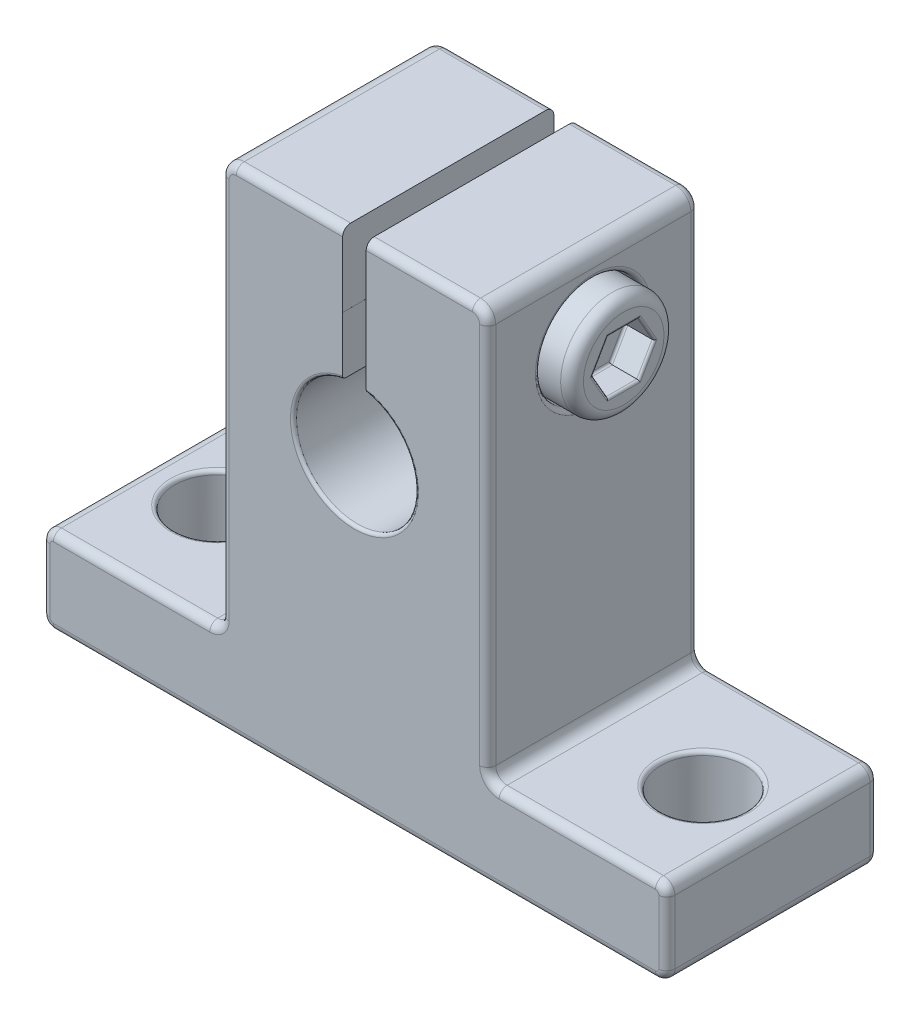
SolidWorks part; units mm, degrees
ref_plane "Plano frontal" through (0, 0, 0) normal (0, 0, 1) x (1, 0, 0)
ref_plane "Plano superior" through (0, 0, 0) normal (0, 1, 0) x (1, 0, 0)
ref_plane "Plano direito" through (0, 0, 0) normal (1, 0, 0) x (0, 0, -1)
sketch "Esboço1" plane through (0, 0, 0) normal (0, 0, 1) x (1, 0, 0)
  line L0 (-7.7757, 16.3) -> (-0.7757, 16.3)
  line L1 (-19.815, -16.3) -> (19.815, -16.3)
  line L2 (-20.565, -15.55) -> (-20.565, -11.35)
  line L3 (-19.815, -10.6) -> (-9.5257, -10.6)
  line L4 (20.565, -15.55) -> (20.565, -11.35)
  line L5 (0.7743, 16.3) -> (7.7743, 16.3)
  line L6 (9.5243, -10.6) -> (19.815, -10.6)
  line L7 (8.7743, 15.3) -> (8.7743, -9.85)
  line L8 (-8.7757, 15.3) -> (-8.7757, -9.85)
  line L10 (-0.7757, 11.4644) -> (-0.7757, 16.3)
  line L12 (0.7743, 11.4644) -> (0.7743, 16.3)
  arc A0 (8.7743, 15.3) -> (7.7743, 16.3) centre (7.7743, 15.3) ccw
  arc A1 (-7.7757, 16.3) -> (-8.7757, 15.3) centre (-7.7757, 15.3) ccw
  arc A2 (-20.565, -15.55) -> (-19.815, -16.3) centre (-19.815, -15.55) ccw
  arc A3 (-20.565, -11.35) -> (-19.815, -10.6) centre (-19.815, -11.35) cw
  arc A4 (19.815, -10.6) -> (20.565, -11.35) centre (19.815, -11.35) cw
  arc A5 (19.815, -16.3) -> (20.565, -15.55) centre (19.815, -15.55) ccw
  arc A6 (8.7743, -9.85) -> (9.5243, -10.6) centre (9.5243, -9.85) ccw
  arc A7 (-8.7757, -9.85) -> (-9.5257, -10.6) centre (-9.5257, -9.85) cw
  arc A8 (-0.7757, 11.4644) -> (0.7743, 11.4644) centre (-0.0007, 7.53) ccw
  point P0 (0, 0)
  point P9 (8.7743, 16.3)
  point P15 (-8.7757, 16.3)
  point P18 (-20.565, -16.3)
  point P23 (20.565, -10.6)
  point P26 (20.565, -16.3)
  point P29 (8.7743, -10.6)
  dimension "D1" = 1
  dimension "D4" = 0.75
  dimension "D6" = 8.02
  dimension "D2" = 41.13
  dimension "D3" = 17.55
  dimension "D5" = 5.7
extrude "Ressalto-extrusão1" add sketch "Esboço1" along normal blind 13.9
fillet "Filete2" radius 0.53 34 edges at (-4.2757, 16.3, 13.9) (-8.4828, 16.0071, 13.9) (4.2743, 16.3, 13.9) (8.4814, 16.0071, 13.9) (8.7743, 2.725, 13.9) (8.994, -10.3803, 13.9) (14.6697, -10.6, 13.9) (20.3453, -10.8197, 13.9) (20.565, -13.45, 13.9) (20.3453, -16.0803, 13.9) (0, -16.3, 13.9) (-20.3453, -16.0803, 13.9) (-20.565, -13.45, 13.9) (-20.3453, -10.8197, 13.9) (-14.6703, -10.6, 13.9) (-8.9954, -10.3803, 13.9) (-4.2757, 16.3, 0) (-8.4828, 16.0071, 0) (4.2743, 16.3, 0) (8.4814, 16.0071, 0) (8.7743, 2.725, 0) (8.994, -10.3803, 0) (14.6697, -10.6, 0) (20.3453, -10.8197, 0) (20.565, -13.45, 0) (20.3453, -16.0803, 0) (0, -16.3, 0) (-20.3453, -16.0803, 0) (-20.565, -13.45, 0) (-20.3453, -10.8197, 0) (-14.6703, -10.6, 0) (-8.9954, -10.3803, 0) (-8.7757, 2.725, 13.9) (-8.7757, 2.725, 0)
sketch "Esboço9" plane through (0, 0, 0) normal (0, 0, -1) x (-1, 0, 0)
  circle A1 centre (0.0007, 7.53) radius 4.01
extrude "Ressalto-extrusão4" add sketch "Esboço9" against normal blind 13.9
sketch "Esboço10" plane through (0, 0, 13.9) normal (0, 0, 1) x (1, 0, 0)
  line L0 (-0.7743, 16.3) -> (-0.7743, 7.6445)
  line L1 (0.7743, 11.4644) -> (0.7743, 7.6445)
  line L3 (-0.7743, 16.3) -> (0.7743, 16.3)
  line L4 (0.7743, 11.4644) -> (0.7743, 16.3)
  line L5 (0.7743, 11.4644) -> (0.7743, 16.3)
  line L8 (0.7743, 11.4644) -> (0.7743, 16.3)
  arc A0 (-0.7743, 7.6445) -> (0.7743, 7.6445) centre (0, 3.71) ccw
  dimension "D1" = 8.02
extrude "Corte-extrusão8" cut sketch "Esboço10" against normal blind 20.9 and the other way blind 16 contours L0 A0 L1 | L4 L3 L0 region at (0, 5.4398, 13.9)
fillet "Filete12" radius 0.2 1 edges at (0, -0.3, 0)
fillet "Filete13" radius 0.2 1 edges at (0, -0.3, 13.9)
sketch "Esboço14" plane through (-8.7757, 0, 0) normal (-1, 0, 0) x (0, 0, 1)
  circle A0 centre (6.95, 11.144) radius 1.71
  dimension "D1" = 3.42
extrude "Corte-extrusão9" cut sketch "Esboço14" against normal blind 20.9
fillet "Filete14" radius 0.2 1 edges at (-8.7757, 9.434, 6.95)
sketch "Esboço15" plane through (8.7743, 0, 0) normal (1, 0, 0) x (0, 0, -1)
  circle A0 centre (-6.95, 11.144) radius 3.5
  dimension "D1" = 7
extrude "Corte-extrusão10" cut sketch "Esboço15" against normal blind 3.9
fillet "Filete16" radius 0.3 1 edges at (8.7743, 14.644, 6.95)
sketch "Esboço16" plane through (4.8743, 0, 0) normal (1, 0, 0) x (0, 0, -1)
  circle A0 centre (-6.95, 11.144) radius 3.4
  dimension "D1" = 6.8
extrude "Ressalto-extrusão5" add sketch "Esboço16" along normal blind 5.9
fillet "Filete19" radius 0.75 2 edges at (4.8743, 14.544, 6.95) (10.7743, 14.544, 6.95)
sketch "Esboço17" plane through (10.7743, 0, 0) normal (1, 0, 0) x (0, 0, -1)
  line L1 (-4.9293, 11.144) -> (-5.9396, 12.894)
  line L2 (-5.9396, 12.894) -> (-7.9604, 12.894)
  line L3 (-7.9604, 12.894) -> (-8.9707, 11.144)
  line L4 (-8.9707, 11.144) -> (-7.9604, 9.394)
  line L5 (-7.9604, 9.394) -> (-5.9396, 9.394)
  line L6 (-5.9396, 9.394) -> (-4.9293, 11.144)
  circle A0 centre (-6.95, 11.144) radius 1.75 construction
  point P1 (-6.95, 9.394)
  dimension "D1" = 3.5
extrude "Corte-extrusão11" cut sketch "Esboço17" against normal blind 1.9
fillet "Filete20" radius 0.15 12 edges at (10.7743, 12.019, 5.4345) (10.7743, 12.894, 6.95) (10.7743, 12.019, 8.4655) (10.7743, 10.269, 8.4655) (10.7743, 9.394, 6.95) (10.7743, 10.269, 5.4345) (8.8743, 9.394, 6.95) (8.8743, 10.269, 8.4655) (8.8743, 12.019, 8.4655) (8.8743, 12.894, 6.95) (8.8743, 12.019, 5.4345) (8.8743, 10.269, 5.4345)
sketch "Esboço18" plane through (4.8743, 0, 0) normal (-1, 0, 0) x (0, 0, 1)
  circle A0 centre (6.95, 11.144) radius 1.7
  dimension "D1" = 3.4
extrude "Ressalto-extrusão6" add sketch "Esboço18" along normal blind 12.9
sketch "Esboço19" plane through (0, -16.3, 0) normal (0, -1, 0) x (1, 0, 0)
  circle A0 centre (-16, 6.95) radius 2.79
  circle A1 centre (16, 6.95) radius 2.79
  point P10 (0, 0)
  dimension "D2" = 5.58
  dimension "D3" = 5.58
  dimension "D1" = 32
extrude "Corte-extrusão12" cut sketch "Esboço19" along normal blind 7.9 and the other way blind 17
fillet "Filete21" radius 0.25 1 edges at (18.79, -10.6, 6.95)
fillet "Filete22" radius 0.25 3 edges at (-16, -16.3, 9.74) (16, -16.3, 9.74) (-16, -10.6, 4.16)
